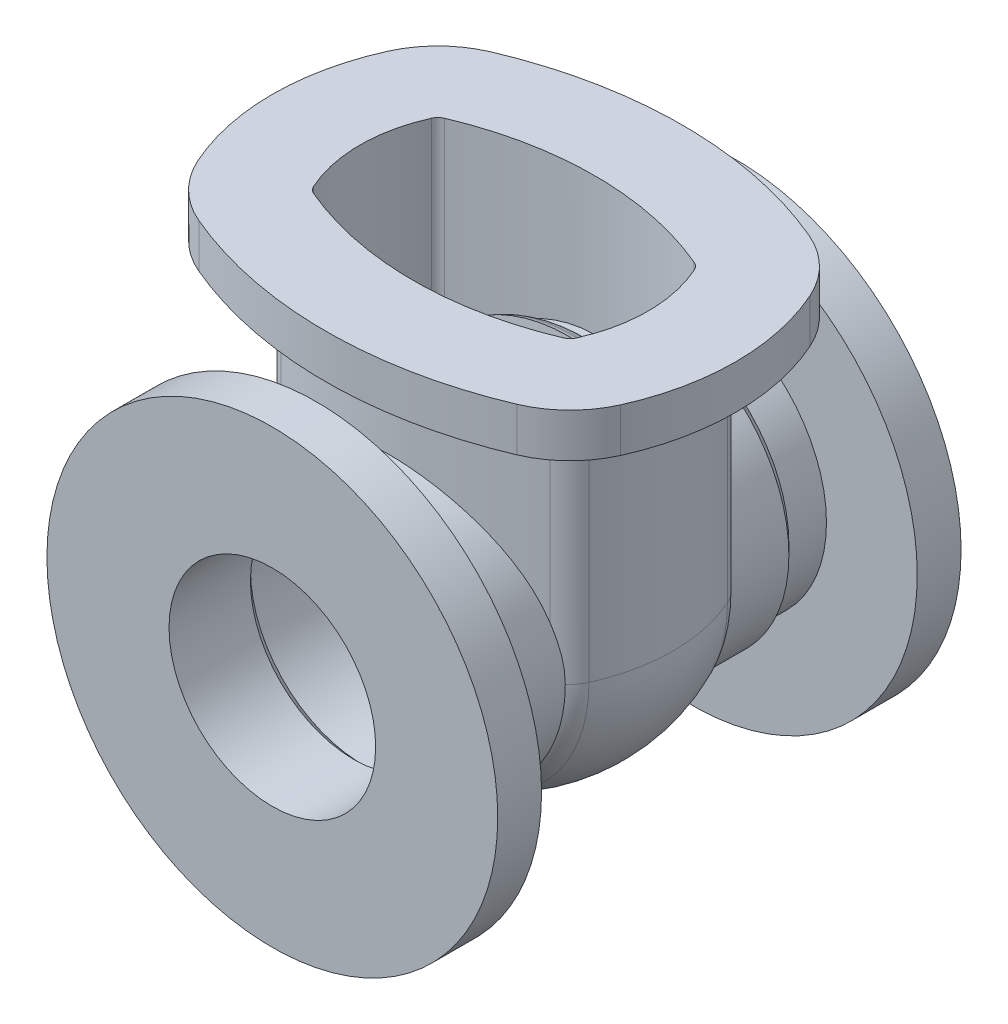
SolidWorks part; units mm, degrees
ref_plane "Front Plane" through (0, 0, 0) normal (0, 0, 1) x (1, 0, 0)
ref_plane "Top Plane" through (0, 0, 0) normal (0, 1, 0) x (1, 0, 0)
ref_plane "Right Plane" through (0, 0, 0) normal (1, 0, 0) x (0, 0, -1)
sketch "Sketch1" plane through (0, 0, 0) normal (1, 0, 0) x (0, 0, -1)
  line L0 (-117.475, 0) -> (0, 0) construction
  line L1 (-117.475, -52.3875) -> (-117.475, -114.3)
  line L2 (-117.475, -114.3) -> (-95.25, -114.3)
  line L3 (-95.25, -114.3) -> (-95.25, -68.2625)
  line L4 (-95.25, -68.2625) -> (-76.2, -68.2625)
  line L5 (-76.2, -68.2625) -> (-71.4375, -73.025)
  line L6 (-71.4375, -73.025) -> (-41.9367, -73.025)
  line L7 (-117.475, -52.3875) -> (-76.2, -52.3875)
  line L8 (-76.2, -52.3875) -> (-71.4375, -57.15)
  line L9 (-71.4375, -57.15) -> (-49.1209, -57.15)
  line L10 (0, 0) -> (0, -73.025) construction
  line L11 (71.4375, -57.15) -> (49.1209, -57.15)
  line L12 (76.2, -52.3875) -> (71.4375, -57.15)
  line L13 (117.475, -52.3875) -> (76.2, -52.3875)
  line L14 (71.4375, -73.025) -> (41.9367, -73.025)
  line L15 (76.2, -68.2625) -> (71.4375, -73.025)
  line L16 (95.25, -68.2625) -> (76.2, -68.2625)
  line L17 (95.25, -114.3) -> (95.25, -68.2625)
  line L18 (117.475, -114.3) -> (95.25, -114.3)
  line L19 (117.475, -52.3875) -> (117.475, -114.3)
  line L20 (-49.1209, -57.15) -> (-35.6169, -57.15)
  line L21 (49.1209, -57.15) -> (35.6169, -57.15)
  arc A0 (0, -73.025) -> (-29.9031, -66.6217) centre (0, 0) cw
  arc A1 (-35.6169, -57.15) -> (-33.1473, -63.3113) centre (115.8875, 0) ccw
  arc A2 (-33.1473, -63.3113) -> (-29.9031, -66.6217) centre (-27.3028, -60.8285) ccw
  arc A3 (0, -85.725) -> (-35.1036, -78.2081) centre (0, 0) cw
  arc A4 (-44.8363, -68.2769) -> (-35.1036, -78.2081) centre (-27.3028, -60.8285) ccw
  arc A5 (-49.1209, -57.15) -> (-44.8363, -68.2769) centre (115.8875, 0) ccw
  arc A6 (35.6169, -57.15) -> (33.1473, -63.3113) centre (-115.8875, 0) cw
  arc A7 (49.1209, -57.15) -> (44.8363, -68.2769) centre (-115.8875, 0) cw
  arc A8 (44.8363, -68.2769) -> (35.1036, -78.2081) centre (27.3028, -60.8285) cw
  arc A9 (0, -85.725) -> (35.1036, -78.2081) centre (0, 0) ccw
  arc A10 (33.1473, -63.3113) -> (29.9031, -66.6217) centre (27.3028, -60.8285) cw
  arc A11 (0, -73.025) -> (29.9031, -66.6217) centre (0, 0) ccw
  arc A12 (-46.0375, 0) -> (-33.1473, -63.3113) centre (115.8875, 0) ccw construction
  arc A13 (-58.7375, 0) -> (-44.8363, -68.2769) centre (115.8875, 0) ccw construction
  dimension "D2" = 73.025
  dimension "D3" = 161.925
  dimension "D4" = 115.8875
  dimension "D5" = 6.35
  dimension "D1" = 117.475
  dimension "D6" = 114.3
  dimension "D7" = 15.875
  dimension "D8" = 15.875
  dimension "D9" = 19.05
  dimension "D10" = 4.7625
  dimension "D11" = 135
  dimension "D12" = 52.3875
  dimension "D13" = 22.225
  dimension "D14" = 12.7
revolve "Revolve1" add sketch "Sketch1" angle 360 about L0 region at (0, -53.3642, 96.8375) region at (0, -73.1685, 0) region at (0, -71.2664, -44.3943)
sketch "Sketch8" plane through (0, 0, 0) normal (0, 1, 0) x (1, 0, 0)
  line L0 (-73.025, -41.9367) -> (-73.025, 41.9367)
  line L3 (0, -117.475) -> (0, 117.475) construction
  line L4 (-114.3, -117.475) -> (114.3, -117.475) construction
  line L5 (114.3, 117.475) -> (-114.3, 117.475) construction
  arc A2 (-73.025, 41.9367) -> (-78.2081, 35.1036) centre (-60.8285, 27.3028) ccw construction
  arc A3 (-78.2081, -35.1036) -> (-73.025, -41.9367) centre (-60.8285, -27.3028) ccw construction
  arc A4 (-78.2081, 35.1036) -> (-78.2081, -35.1036) centre (0, 0) ccw construction
  arc A5 (-73.025, 41.9367) -> (-78.2081, 35.1036) centre (-60.8285, 27.3028) ccw
  arc A6 (-78.2081, -35.1036) -> (-73.025, -41.9367) centre (-60.8285, -27.3028) ccw
  arc A7 (-78.2081, 35.1036) -> (-78.2081, -35.1036) centre (0, 0) ccw
sketch "Sketch2" plane through (0, 0, 0) normal (1, 0, 0) x (0, 0, -1)
  line L0 (0, -85.725) -> (0, 85.725) construction
  line L1 (-25.4, 0) -> (-35.4, 114.3)
  line L2 (-35.4, 114.3) -> (35.4, 114.3)
  line L3 (25.4, 0) -> (-25.4, 0) construction
  line L4 (-25.4, 0) -> (25.4, 0)
  line L5 (25.4, 0) -> (35.4, 114.3)
  arc A0 (-35.1036, -78.2081) -> (35.1036, -78.2081) centre (0, 0) ccw construction
  arc A1 (35.1036, 78.2081) -> (-35.1036, 78.2081) centre (0, 0) ccw construction
  point P14 (0, 114.3)
  dimension "D1" = 5
  dimension "D2" = 25.4
extrude "Cut-Extrude1" cut sketch "Sketch2" against normal through all both and the other way through all
ref_plane "Plane1" through (0, 142.875, 0) normal (0, 1, 0) x (1, 0, 0)
sketch "Sketch3" plane through (0, 142.875, 0) normal (0, 1, 0) x (1, 0, 0)
  line L0 (-73.025, 0) -> (85.725, 0) construction
  line L1 (0, 0) -> (0, 35.1036) construction
  line L2 (78.2081, 35.1036) -> (-78.2081, 35.1036) construction
  arc A0 (-68.4653, 25.4) -> (-68.4653, -25.4) centre (0, 0) ccw construction
  arc A1 (81.8756, -25.4) -> (81.8756, 25.4) centre (0, 0) ccw construction
  arc A2 (-66.6217, -29.9031) -> (-66.6217, 29.9031) centre (0, 0) cw
  arc A3 (63.3113, 33.1473) -> (-63.3113, 33.1473) centre (0, -115.8875) ccw
  arc A4 (-66.6217, 29.9031) -> (-63.3113, 33.1473) centre (-60.8285, 27.3028) cw
  arc A5 (80.6909, 74.0588) -> (-80.6909, 74.0588) centre (0, -115.8875) ccw
  arc A6 (66.6217, -29.9031) -> (66.6217, 29.9031) centre (0, 0) ccw
  arc A7 (66.6217, 29.9031) -> (63.3113, 33.1473) centre (60.8285, 27.3028) ccw
  arc A8 (66.6217, -29.9031) -> (63.3113, -33.1473) centre (60.8285, -27.3028) cw
  arc A9 (-66.6217, -29.9031) -> (-63.3113, -33.1473) centre (-60.8285, -27.3028) ccw
  arc A10 (63.3113, -33.1473) -> (-63.3113, -33.1473) centre (0, 115.8875) cw
  arc A11 (-107.1741, 48.105) -> (-80.6909, 74.0588) centre (-60.8285, 27.3028) cw
  arc A12 (-107.1741, -48.105) -> (-107.1741, 48.105) centre (0, 0) cw
  arc A13 (-107.1741, -48.105) -> (-80.6909, -74.0588) centre (-60.8285, -27.3028) ccw
  arc A14 (80.6909, -74.0588) -> (-80.6909, -74.0588) centre (0, 115.8875) cw
  arc A15 (107.1741, -48.105) -> (80.6909, -74.0588) centre (60.8285, -27.3028) cw
  arc A16 (107.1741, -48.105) -> (107.1741, 48.105) centre (0, 0) ccw
  arc A17 (107.1741, 48.105) -> (80.6909, 74.0588) centre (60.8285, 27.3028) ccw
  arc A18 (68.2769, 44.8363) -> (-68.2769, 44.8363) centre (0, -115.8875) ccw
  arc A19 (-78.2081, 35.1036) -> (-68.2769, 44.8363) centre (-60.8285, 27.3028) cw
  arc A20 (-78.2081, -35.1036) -> (-78.2081, 35.1036) centre (0, 0) cw
  arc A21 (-78.2081, -35.1036) -> (-68.2769, -44.8363) centre (-60.8285, -27.3028) ccw
  arc A22 (68.2769, -44.8363) -> (-68.2769, -44.8363) centre (0, 115.8875) cw
  arc A23 (78.2081, -35.1036) -> (68.2769, -44.8363) centre (60.8285, -27.3028) cw
  arc A24 (78.2081, -35.1036) -> (78.2081, 35.1036) centre (0, 0) ccw
  arc A25 (78.2081, 35.1036) -> (68.2769, 44.8363) centre (60.8285, 27.3028) ccw
  point P3 (0, 35.1036)
  point P25 (-73.025, 0)
  dimension "D1" = 161.925
  dimension "D3" = 6.35
  dimension "D4" = 73.025
  dimension "D2" = 115.8875
  dimension "D5" = 44.45
  dimension "D6" = 12.7
extrude "Boss-Extrude1" add sketch "Sketch3" against normal up to surface (142.875 mm away) contours A24 A25 A18 A19 A20 A21 A22 A23 A8 A10 A9 A2 A4 A3 A7 A6 region at (72.7076, 142.875, -39.4241) up to face at (-77.2727, 0, 0)
extrude "Boss-Extrude2" add sketch "Sketch3<3>" against normal blind 22.225 contours A16 A17 A5 A11 A12 A13 A14 A15 A25 A24 A23 A22 A21 A20 A19 A18 region at (94.3094, 142.875, -61.4665)
sketch "Sketch3<3>" plane through (0, 142.875, 0) normal (0, 1, 0) x (1, 0, 0) same geometry as "Sketch3"
sketch "Sketch5" plane through (0, 0, 0) normal (0, 0, 1) x (1, 0, 0)
  line L1 (-57.15, 0) -> (57.15, 0)
  line L2 (-57.15, 0) -> (57.15, 0)
  arc A1 (57.15, 0) -> (-57.15, 0) centre (0, 0) ccw
  arc A2 (57.15, 0) -> (-57.15, 0) centre (0, 0) ccw
  dimension "D1" = 0
extrude "Cut-Extrude2" cut sketch "Sketch5" along normal up to next and the other way up to next
